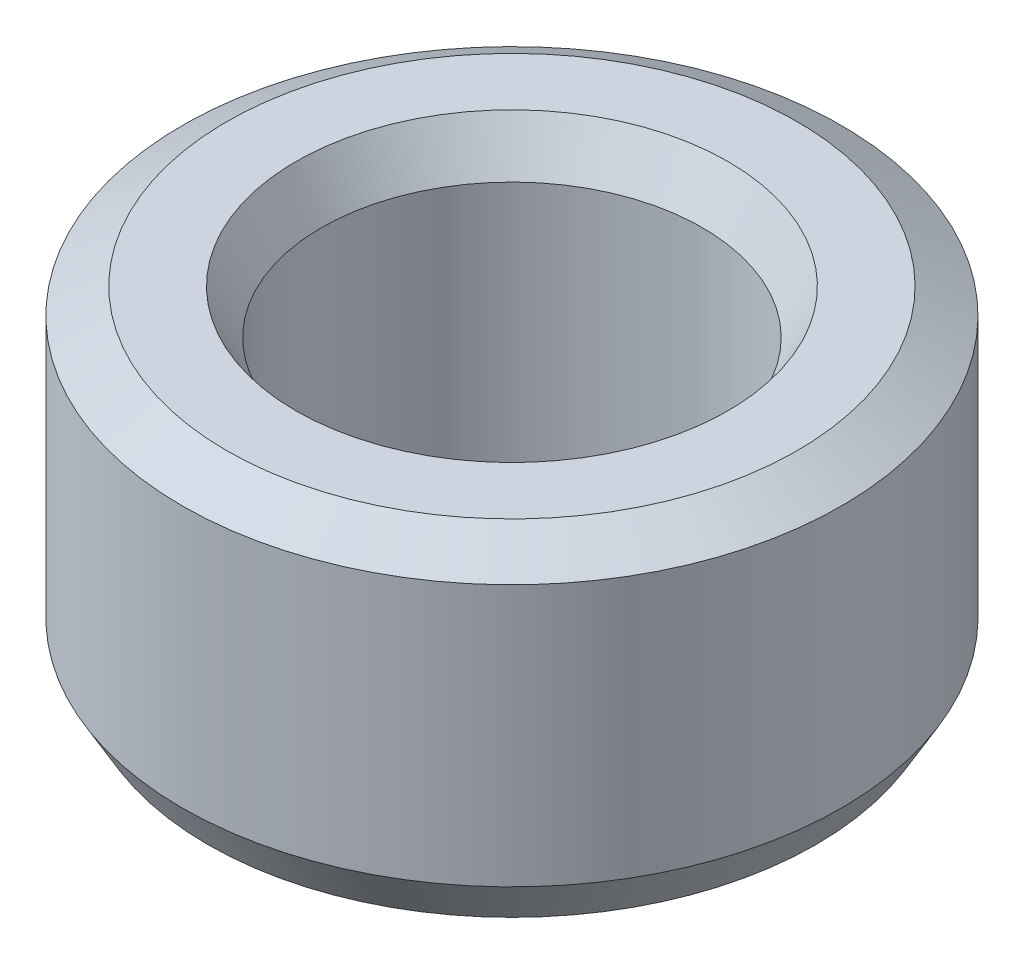
SolidWorks part; units mm, degrees
ref_plane "Front Plane" through (0, 0, 0) normal (0, 0, 1) x (1, 0, 0)
ref_plane "Top Plane" through (0, 0, 0) normal (0, 1, 0) x (1, 0, 0)
ref_plane "Right Plane" through (0, 0, 0) normal (1, 0, 0) x (0, 0, -1)
sketch "Sketch1" plane through (0, 0, 0) normal (0, 1, 0) x (1, 0, 0)
  circle A0 centre (0, 0) radius 27.5
  dimension "SLEEVE_OD" = 55
extrude "Boss-Extrude1" add sketch "Sketch1" along normal blind 27.6773
sketch "Sketch2" plane through (0, 0, 0) normal (0, 1, 0) x (1, 0, 0)
  circle A0 centre (0, 0) radius 15.8889
  dimension "BORE_D" = 31.7779
extrude "Cut-Extrude1" cut sketch "Sketch2" along normal through all
chamfer "Chamfer1" distance 2.1344 angle 60.099 4 edges at (0, 27.6773, 15.8889) (0, 0, 15.8889) (0, 0, 27.5) (0, 27.6773, 27.5) first distance on face at (0, 27.6773, 15.8889) first distance on face at (0, 0, 15.8889) first distance on face at (0, 27.6773, 27.5)
